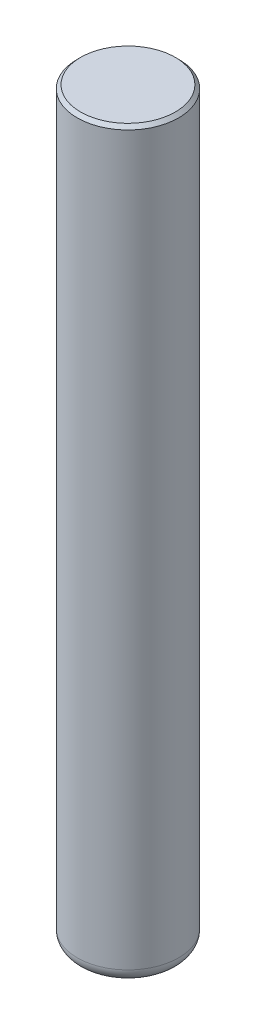
SolidWorks part; units mm, degrees
material "6061-T6 Aluminum"
ref_plane "Front Plane" through (0, 0, 0) normal (0, 0, 1) x (1, 0, 0)
ref_plane "Top Plane" through (0, 0, 0) normal (0, 1, 0) x (1, 0, 0)
ref_plane "Right Plane" through (0, 0, 0) normal (1, 0, 0) x (0, 0, -1)
sketch "Sketch1" plane through (0, 0, 0) normal (0, 1, 0) x (1, 0, 0)
  circle A0 centre (0, 0) radius 15
  dimension "D1" = 30
extrude "Boss-Extrude1" add sketch "Sketch1" along normal blind 220
fillet "Fillet1" radius 4 1 edges at (0, 0, 15)
chamfer "Chamfer1" distance 1 angle 45 1 edges at (0, 220, 15)
